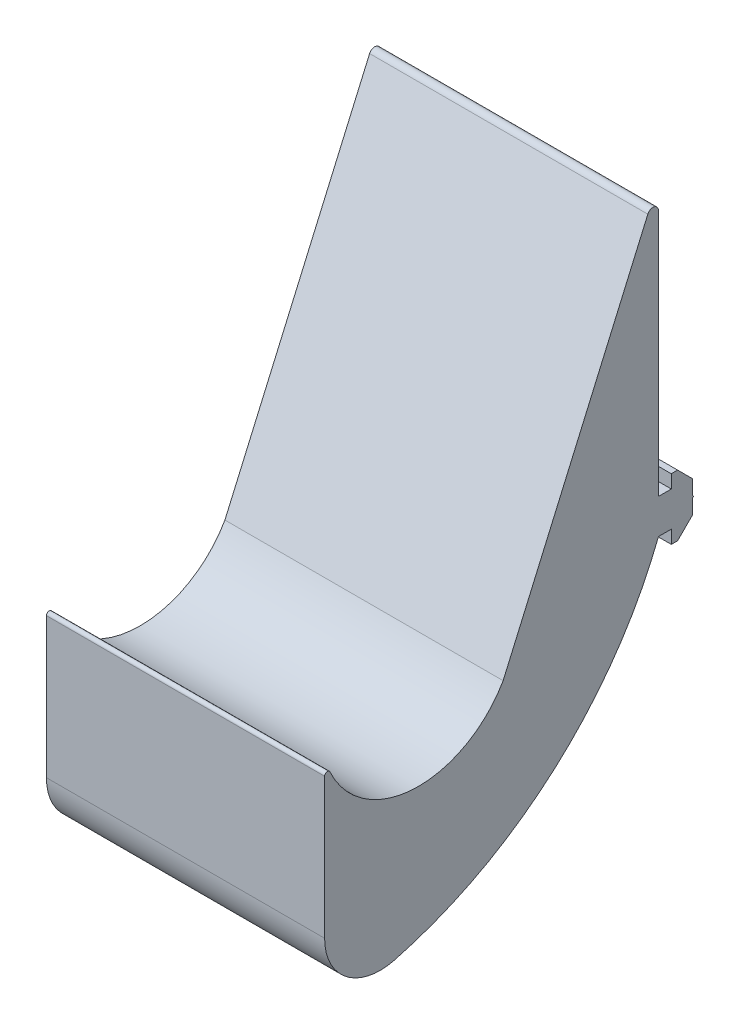
SolidWorks part; units mm, degrees
ref_plane "Front Plane" through (0, 0, 0) normal (0, 0, 1) x (1, 0, 0)
ref_plane "Top Plane" through (0, 0, 0) normal (0, 1, 0) x (1, 0, 0)
ref_plane "Right Plane" through (0, 0, 0) normal (1, 0, 0) x (0, 0, -1)
sketch "Sketch1" plane through (0, 0, 0) normal (1, 0, 0) x (0, 0, -1)
  line L1 (-30, -50) -> (30, -50)
  line L2 (-30, -50) -> (-30, -10)
  line L4 (30, -50) -> (30, 50)
  line L5 (-30, -50) -> (-13.7001, -22.8334) construction
  line L6 (4.7396, -7.8994) -> (30, -50) construction
  line L8 (2.0799, -13.9958) -> (30, 50)
  arc A0 (-30, -10) -> (2.0799, -13.9958) centre (-13.1311, -5.3427) ccw
  point P0 (0, 0)
  dimension "D3" = 17.5
  dimension "D1" = 60
  dimension "D2" = 40
  dimension "D4" = 100
  dimension "D5" = 23.571
  dimension "D6" = 34.7396
  dimension "D7" = 6.6514
extrude "Boss-Extrude1" add sketch "Sketch1" along normal blind 50
fillet "Fillet1" radius 1 1 edges at (25, 50, -30)
fillet "Fillet2" radius 0.5 1 edges at (25, -10, 30)
sketch "Sketch2" plane through (50, 0, 0) normal (1, 0, 0) x (0, 0, -1)
  line L0 (30, 0.7286) -> (32.3, 0.7286)
  line L1 (30, -5.5214) -> (30, -7.8964)
  line L2 (30, -5.5214) -> (32.3, -5.5214)
  line L3 (32.3, -5.5214) -> (32.3, -7.8964)
  line L4 (-30, -12.83) -> (-30, -50)
  line L5 (-30, -50) -> (30, -50)
  line L6 (30, -50) -> (30, 45.2072)
  line L7 (28.0834, 45.607) -> (2.0799, -13.9958)
  line L8 (-30, -12.83) -> (-30, -50)
  line L9 (-30, -50) -> (30, -50)
  line L10 (30, -50) -> (30, 45.2072)
  line L11 (28.0834, 45.607) -> (2.0799, -13.9958)
  line L12 (30, -7.8964) -> (32.3, -7.8964)
  line L13 (32.3, 0.7286) -> (32.3, 3.1036)
  arc A3 (-29.0453, -12.622) -> (2.0799, -13.9958) centre (-13.1311, -5.3427) ccw
  arc A4 (-29.0453, -12.622) -> (-30, -12.83) centre (-29.5, -12.83) ccw
  arc A5 (30, 45.2072) -> (28.0834, 45.607) centre (29, 45.2072) ccw
  arc A6 (-29.0453, -12.622) -> (2.0799, -13.9958) centre (-13.1311, -5.3427) ccw
  arc A7 (-29.0453, -12.622) -> (-30, -12.83) centre (-29.5, -12.83) ccw
  arc A8 (30, 45.2072) -> (28.0834, 45.607) centre (29, 45.2072) ccw
  point P17 (0, 0)
  point P18 (30, -2.3964)
  line B0 (40, -2.3964) -> (30, -2.3964) construction
  line B1 (36.31, -2.3964) -> (36.1, -2.6064)
  line B2 (36.1, -2.6064) -> (36.1, -5.2358)
  line B3 (36.1, -5.2358) -> (33.4393, -7.8964)
  line B4 (33.4393, -7.8964) -> (31.8, -7.8964)
  line B5 (31.8, -7.8964) -> (31.8, -5.5214)
  line B6 (31.8, -5.5214) -> (31.455, -5.5214)
  line B7 (31.455, -5.5214) -> (30, -6.9764)
  line B8 (30, -6.9764) -> (30, 2.1836)
  line B9 (40, -2.3964) -> (34.0868, -8.3096) construction
  line B10 (31.455, 0.7286) -> (30, 2.1836)
  line B11 (31.8, 0.7286) -> (31.455, 0.7286)
  line B12 (31.8, 3.1036) -> (31.8, 0.7286)
  line B13 (33.4393, 3.1036) -> (31.8, 3.1036)
  line B14 (36.1, 0.4429) -> (33.4393, 3.1036)
  line B15 (36.1, -2.1864) -> (36.1, 0.4429)
  line B16 (36.31, -2.3964) -> (36.1, -2.1864)
  line M15 (30, -50) -> (30, 45.2072)
  dimension "D1" = 0
sketch_block_instance "V Slot 1-4"
sketch_block "V Slot 1" parameters "D1"=10, "D2"=11, "D3"=4.3, "D4"=1.8, "D5"=0.21, "D6"=45, "D7"=9.16, "D8"=1.5, "D9"=6.25
extrude "Boss-Extrude2" add sketch "Sketch2" against normal blind 50 contours B1 B16 B15 B14 B13 L13 L0 L2 L3 B4 B3 B2 M15 region at (50, -2.3964, -33.1636)
fillet "Fillet3" radius 70 1 edges at (25, -50, -30)
fillet "Fillet4" radius 10 1 edges at (25, -49.8079, 30)
